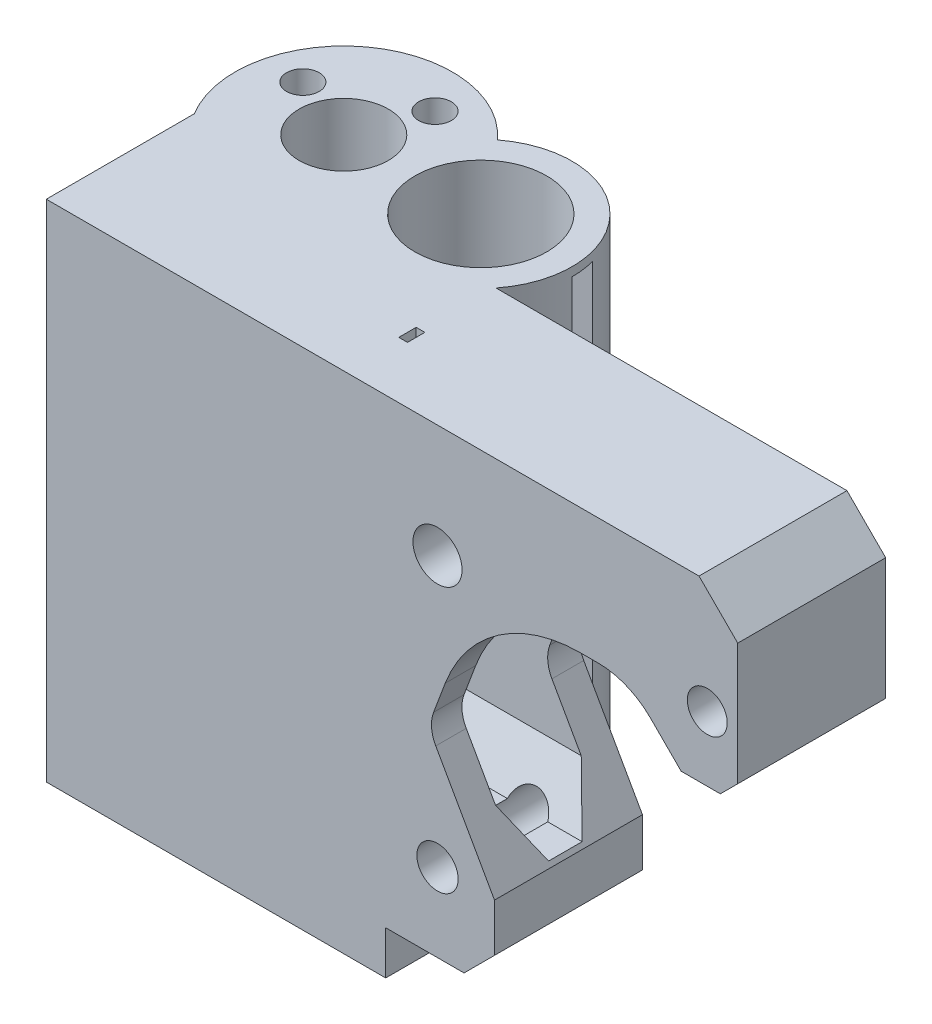
SolidWorks part; units mm, degrees
ref_plane "Front Plane" through (0, 0, 0) normal (0, 0, 1) x (1, 0, 0)
ref_plane "Top Plane" through (0, 0, 0) normal (0, 1, 0) x (1, 0, 0)
ref_plane "Right Plane" through (0, 0, 0) normal (1, 0, 0) x (0, 0, -1)
sketch "Sketch1" plane through (0, 0, 0) normal (0, 0, 1) x (1, 0, 0)
  line L0 (39, -53) -> (48, -53)
  line L1 (0, 0) -> (39, 0)
  line L2 (0, 0) -> (0, -58)
  line L3 (0, -58) -> (39, -58)
  line L4 (39, -53) -> (39, -58)
  line L5 (39, 0) -> (75, 0)
  line L6 (75, 0) -> (79.45, -4.45)
  line L7 (79.45, -4.45) -> (79.45, -18.45)
  line L8 (79.45, -18.45) -> (77.45, -20.45)
  line L9 (77.45, -20.45) -> (72.95, -20.45)
  line L10 (72.95, -20.45) -> (69.45, -16.95)
  line L12 (45.8405, -25.2376) -> (44.5009, -28.8048)
  line L13 (44.75, -32.0294) -> (51.5, -44)
  line L14 (51.5, -44) -> (51.5, -49.5)
  line L15 (61.4145, -14.45) -> (63.4145, -14.45)
  line L16 (51.5, -49.5) -> (48, -53)
  arc A5 (63.4145, -14.45) -> (69.45, -16.95) centre (63.4145, -22.9855) cw
  arc A6 (61.4145, -14.45) -> (45.8405, -25.2376) centre (61.4145, -31.0859) ccw
  arc A7 (44.5009, -28.8048) -> (44.75, -32.0294) centre (48.083, -30.15) ccw
  dimension "D1" = 58
  dimension "D2" = 39
  dimension "D3" = 75
  dimension "D4" = 4.45
  dimension "D5" = 135
  dimension "D6" = 14
  dimension "D7" = 2
  dimension "D8" = 3.5
  dimension "D9" = 6
  dimension "D10" = 5
  dimension "D11" = 4.5
  dimension "D12" = 130
  dimension "D13" = 3.5
  dimension "D14" = 5.5
  dimension "D15" = 6.75
  dimension "D16" = 9
  dimension "D17" = 13.85
  dimension "D18" = 3.417
  dimension "D19" = 2
extrude "Boss-Extrude1" add sketch "Sketch1" along normal blind 17
sketch "Sketch2" plane through (0, 0, 0) normal (0, 1, 0) x (1, 0, 0)
  line L0 (0, -17) -> (0, 6.5) construction
  line L1 (0, 6.5) -> (26.427, 6.5) construction
  circle A0 centre (26.427, 6.5) radius 10.5
  dimension "D2" = 21
  dimension "D1" = 23.5
  dimension "D3" = 26.427
extrude "Boss-Extrude2" add sketch "Sketch2" against normal up to surface (58 mm away) up to face at (19.5, -58, 8.5)
sketch "Sketch3" plane through (0, 0, 0) normal (0, 1, 0) x (1, 0, 0)
  line L0 (0, -17) -> (0, 20.4292) construction
  line L1 (10.6771, 6.5) -> (0, 6.5) construction
  line L2 (75, -17) -> (0, -17) construction
  circle A0 centre (10.6771, 6.5) radius 12.5
  dimension "D3" = 25
  dimension "D2" = 23.5
extrude "Boss-Extrude3" add sketch "Sketch3" against normal blind 13.5
sketch "Sketch4" plane through (0, 0, 0) normal (0, 1, 0) x (1, 0, 0)
  circle A0 centre (26.427, 6.5) radius 7.575
  circle A1 centre (10.6771, 6.5) radius 5.125
  dimension "D1" = 10.25
  dimension "D2" = 15.15
extrude "Cut-Extrude1" cut sketch "Sketch4" against normal through all
sketch "Sketch5" plane through (0, 0, 0) normal (-1, 0, 0) x (0, 0, 1)
  line L0 (10.5, -43.5) -> (6.65, -43.5)
  line L1 (6.65, -43.5) -> (3.65, -38)
  line L2 (3.65, -38) -> (3.65, -19)
  line L3 (3.65, -19) -> (6.65, -13.5)
  line L4 (6.65, -13.5) -> (10.5, -13.5)
  line L5 (10.5, -13.5) -> (13.5, -19)
  line L6 (13.5, -19) -> (13.5, -38)
  line L7 (13.5, -38) -> (10.5, -43.5)
  line L8 (17, 0) -> (0, 0) construction
  line L9 (17, 0) -> (17, -58) construction
  line L10 (8.5, -6) -> (8.5, -51) construction
  line L11 (8.5, -28.5) -> (38.7948, -28.5) construction
  line L12 (3.65, -38) -> (13.5, -38) construction
  line L13 (3.65, -19) -> (13.5, -19) construction
  circle A0 centre (8.5, -6) radius 4.05
  circle A1 centre (8.5, -51) radius 4.05
  point P24 (4.4414, -29)
  dimension "D8" = 8.1
  dimension "D9" = 8.1
  dimension "D1" = 19
  dimension "D2" = 3
  dimension "D3" = 3.85
  dimension "D4" = 15
  dimension "D5" = 6
  dimension "D6" = 45
  dimension "D7" = 5.5
  dimension "D10" = 5.5
  dimension "D12" = 19
  dimension "D13" = 3.85
  dimension "D14" = 3
  dimension "D15" = 3
  dimension "D16" = 3.5
  dimension "D17" = 8.5
  dimension "D18" = 8.5
extrude "Cut-Extrude2" cut sketch "Sketch5" against normal blind 35
sketch "Sketch6" plane through (0, 0, 0) normal (0, 0, -1) x (-1, 0, 0)
  line L0 (-75.9503, -13) -> (-44.9503, -13) construction
  line L1 (-44.9503, -13) -> (-44.9503, -44) construction
  line L2 (-44.9503, -44) -> (-75.9503, -44) construction
  line L3 (-75.9503, -44) -> (-75.9503, -13) construction
  line L4 (-75.9503, -28.5) -> (-44.9503, -28.5) construction
  line L5 (-60.4503, -13) -> (-60.4503, -44) construction
  line L6 (-53.4306, -6) -> (-40.9864, -6) construction
  line L7 (-75, 0) -> (-34.6732, 0) construction
  line L8 (-60.4503, -51) -> (-40.9864, -51) construction
  line L9 (-40.9864, -6) -> (-40.9864, -51) construction
  line L10 (-40.9864, -28.5) -> (-48.7037, -28.5) construction
  circle A0 centre (-75.9503, -13) radius 2.2933
  circle A1 centre (-44.9503, -13) radius 2.8225
  circle A2 centre (-44.9503, -44) radius 2.3733
  circle A3 centre (-60.4503, -28.5) radius 11 construction
  point P14 (-60.4503, -28.5)
  dimension "D3" = 22
  dimension "D1" = 31
  dimension "D2" = 31
  dimension "D4" = 6
  dimension "D5" = 45
extrude "Cut-Extrude3" cut sketch "Sketch6" against normal through all
sketch "Sketch8" plane through (35, 0, 0) normal (-1, 0, 0) x (0, 0, 1)
  line L8 (10.5, -43.5) -> (13.5, -38)
  line L9 (13.5, -38) -> (13.5, -19)
  line L10 (13.5, -19) -> (10.5, -13.5)
  line L11 (10.5, -13.5) -> (6.65, -13.5)
  line L12 (6.65, -13.5) -> (3.65, -19)
  line L13 (3.65, -19) -> (3.65, -38)
  line L14 (3.65, -38) -> (6.65, -43.5)
  line L15 (6.65, -43.5) -> (10.5, -43.5)
  line L16 (10.5, -43.5) -> (13.5, -38)
  line L17 (13.5, -38) -> (13.5, -19)
  line L18 (13.5, -19) -> (10.5, -13.5)
  line L19 (10.5, -13.5) -> (6.65, -13.5)
  line L20 (6.65, -13.5) -> (3.65, -19)
  line L21 (3.65, -19) -> (3.65, -38)
  line L22 (3.65, -38) -> (6.65, -43.5)
  line L23 (6.65, -43.5) -> (10.5, -43.5)
  dimension "D1" = 0
extrude "Cut-Extrude4" cut sketch "Sketch8" against normal blind 20
sketch "Sketch10" plane through (0, 0, 0) normal (0, 1, 0) x (1, 0, 0)
  line L0 (13.5702, 14.0925) -> (10.6771, 6.5) construction
  line L1 (10.6771, 6.5) -> (3.0846, 9.3931) construction
  circle A0 centre (13.5702, 14.0925) radius 1.875
  circle A1 centre (3.0846, 9.3931) radius 1.875
  dimension "D3" = 3.75
  dimension "D4" = 3.75
  dimension "D1" = 90
  dimension "D2" = 8.125
  dimension "D5" = 8.125
extrude "Cut-Extrude6" cut sketch "Sketch10" against normal through all
sketch "Sketch11" plane through (0, -58, 0) normal (0, -1, 0) x (1, 0, 0)
  line L0 (0, 17) -> (0, 0) construction
  line L1 (35, 8.5) -> (34, 8.5)
  line L2 (35, 8.5) -> (35, 10.5)
  line L3 (35, 10.5) -> (34, 10.5)
  line L4 (34, 8.5) -> (34, 10.5)
  line L5 (0, 17) -> (39, 17) construction
  dimension "D1" = 35
  dimension "D2" = 1
  dimension "D3" = 2
  dimension "D4" = 6.5
extrude "Cut-Extrude7" cut sketch "Sketch11" against normal blind 8
ref_plane "Plane1" through (0, -29, 0) normal (0, 1, 0) x (1, 0, 0)
mirror "Mirror1" about plane through (0, -29, 0) normal (0, 1, 0) of "Cut-Extrude7"
sketch "Sketch13" plane through (0, -58, 0) normal (0, -1, 0) x (1, 0, 0)
  line L0 (26.427, -6.5) -> (36.5692, -9.2176) construction
  line L1 (26.427, -6.5) -> (9.2701, -6.5) construction
  line L2 (26.427, -6.5) -> (36.927, -6.5) construction
  line L3 (33.7439, -8.4606) -> (36.5692, -9.2176)
  line L4 (36.927, -6.5) -> (34.002, -6.5)
  arc A0 (33.7439, -8.4606) -> (34.002, -6.5) centre (26.427, -6.5) ccw
  arc A1 (15.927, -6.5) -> (36.927, -6.5) centre (26.427, -6.5) ccw construction
  arc A2 (18.1808, 0) -> (34.6732, 0) centre (26.427, -6.5) ccw construction
  circle A3 centre (26.427, -6.5) radius 7.575 construction
  dimension "D1" = 15
  dimension "D2" = 180
extrude "Cut-Extrude9" cut sketch "Sketch13" against normal blind 57 and the other way through all
